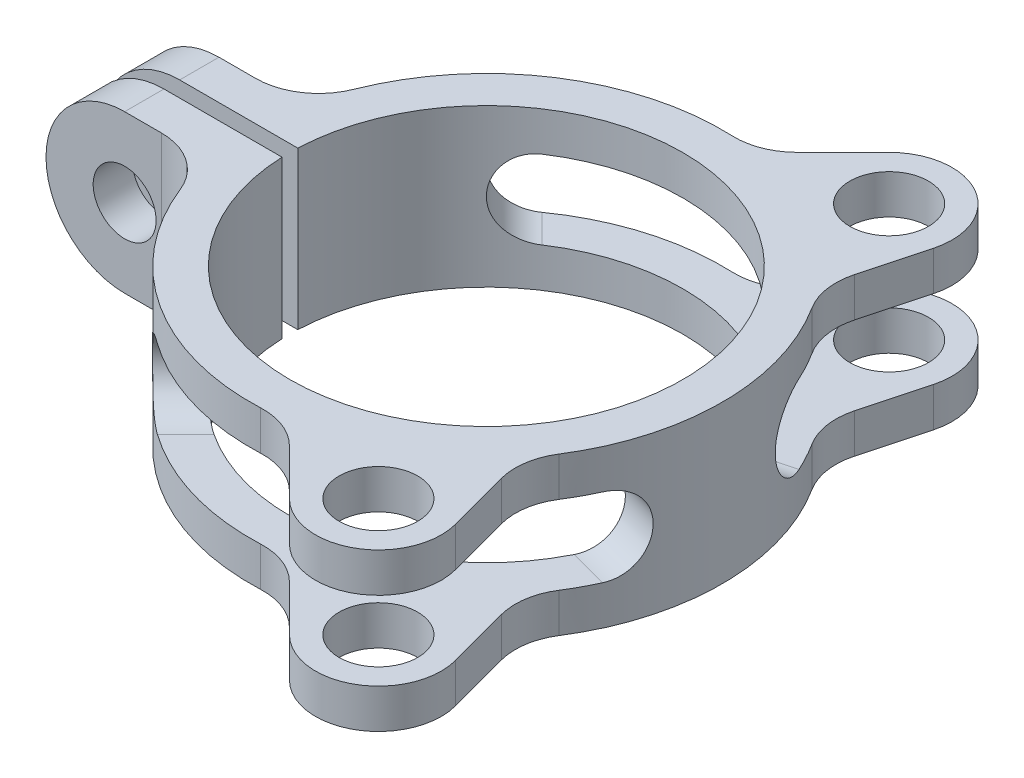
SolidWorks part; units mm, degrees
ref_plane "Front Plane" through (0, 0, 0) normal (0, 0, 1) x (1, 0, 0)
ref_plane "Top Plane" through (0, 0, 0) normal (0, 1, 0) x (1, 0, 0)
ref_plane "Right Plane" through (0, 0, 0) normal (1, 0, 0) x (0, 0, -1)
sketch "Sketch1" plane through (0, 0, 0) normal (0, 1, 0) x (1, 0, 0)
  line L1 (0, 47.8238) -> (0, 0) construction
  line L2 (0, 0) -> (45.4323, 0) construction
  line L3 (0, 0) -> (-50, 0)
  line L4 (26.4774, 30.4054) -> (23.3705, 18.8101)
  line L5 (13.0931, 38.1328) -> (4.6048, 29.6445)
  line L6 (13.0931, -38.1328) -> (4.6048, -29.6445)
  line L7 (26.4774, -30.4054) -> (23.3705, -18.8101)
  line L8 (0, 0) -> (0, 6)
  line L17 (0, 6) -> (-50, 6)
  line L18 (-50, 0) -> (-50, 6)
  line L19 (0, 0) -> (-50, 0)
  line L20 (0, 0) -> (0, -6)
  line L21 (0, -6) -> (-50, -6)
  line L22 (-50, 0) -> (-50, -6)
  circle A0 centre (0, 0) radius 37.5 construction
  circle A2 centre (18.75, 32.476) radius 5
  circle A3 centre (18.75, -32.476) radius 5
  circle A5 centre (18.75, 32.476) radius 8
  circle A6 centre (18.75, -32.476) radius 8
  circle A7 centre (0, 0) radius 25
  circle A8 centre (0, 0) radius 30
  point P15 (0, 0)
  point P21 (0, 0)
  point P35 (0, 0)
  dimension "D1" = 75
  dimension "D2" = 12
  dimension "D4" = 10
  dimension "D6" = 50
  dimension "D7" = 60
  dimension "D5" = 16
  dimension "D8" = 4.6048
  dimension "D9" = 13.0931
  dimension "D3" = 50
  dimension "D10" = 18.75
  dimension "D11" = 23.3705
  dimension "D12" = 26.4774
  dimension "D13" = 18.8101
  dimension "D14" = 29.6445
extrude "Boss-Extrude1" add sketch "Sketch1" along normal blind 20
fillet "Fillet1" radius 8 6 edges at (4.6048, 10, -29.6445) (4.6048, 10, 29.6445) (23.3705, 10, -18.8101) (23.3705, 10, 18.8101) (-29.3939, 10, -6) (-29.3939, 10, 6)
sketch "Sketch8" plane through (0, 0, 0) normal (0, 1, 0) x (1, 0, 0)
  line L2 (18.75, 32.476) -> (0, 0) construction
  line L4 (-54.9284, 54.9284) -> (112.7904, 30.2221)
  line L5 (0, 0) -> (112.7904, 30.2221)
  line L6 (0, 0) -> (-54.9284, 54.9284)
  line L7 (0, 0) -> (42.7833, 0) construction
  line L8 (0, 0) -> (112.7904, -30.2221)
  line L9 (-54.9284, -54.9284) -> (112.7904, -30.2221)
  line L10 (0, 0) -> (-54.9284, -54.9284)
  dimension "D1" = 45
  dimension "D2" = 120
extrude "Cut-Extrude4" cut sketch "Sketch8" along normal blind 10 from offset 5 contours L8 L10 L9 | L6 L5 L4
fillet "Fillet4" radius 5 4 edges at (-17.6777, 10, 17.6777) (-19.4454, 5, 19.4454) (-19.4454, 15, 19.4454) (-21.2132, 10, 21.2132)
fillet "Fillet5" radius 5 4 edges at (28.9778, 10, 7.7646) (24.1481, 10, 6.4705) (26.563, 15, 7.1175) (26.563, 5, 7.1175)
fillet "Fillet6" radius 5 4 edges at (28.9778, 10, -7.7646) (24.1481, 10, -6.4705) (26.563, 5, -7.1175) (26.563, 15, -7.1175)
fillet "Fillet7" radius 5 4 edges at (-17.6777, 10, -17.6777) (-19.4454, 15, -19.4454) (-21.2132, 10, -21.2132) (-19.4454, 5, -19.4454)
sketch "Sketch9" plane through (0, 0, 0) normal (0, 0, 1) x (1, 0, 0)
  line L9 (-40, 20) -> (-50, 20)
  line L10 (-50, 20) -> (-50, 0)
  line L11 (-50, 0) -> (-40, 0)
  line L12 (-35.327, 20) -> (-50, 20) construction
  line L13 (-35.327, 0) -> (-50, 0) construction
  circle A0 centre (-40, 10) radius 4
  circle A1 centre (-40, 10) radius 10
  point P2 (0, 0)
  point P6 (0, 0)
  point P7 (0, 0)
  point P11 (0, 0)
  point P12 (0, 0)
  point P14 (0, 0)
  point P16 (0, 0)
  point P17 (-44.6964, 20.4934)
  point P18 (0, 0)
  point P24 (0, 0)
  point P25 (0, 0)
  point P28 (0, 0)
  point P29 (0, 0)
  dimension "D1" = 8
  dimension "D3" = 20
extrude "Cut-Extrude5" cut sketch "Sketch9" against normal through all both and the other way through all contours A1 L9 L10 | A1 L10 L11 | A0
sketch "Sketch10" plane through (0, 20, 0) normal (0, 1, 0) x (1, 0, 0)
  line L0 (-35.327, 6) -> (-40, 6) construction
  line L1 (-58.653, 1) -> (-18.9067, 1)
  line L2 (-58.653, 1) -> (-58.653, -1)
  line L3 (-58.653, -1) -> (-18.9067, -1)
  line L4 (-18.9067, 1) -> (-18.9067, -1)
  dimension "D1" = 2
  dimension "D2" = 5
extrude "Cut-Extrude6" cut sketch "Sketch10" against normal through all both and the other way through all
